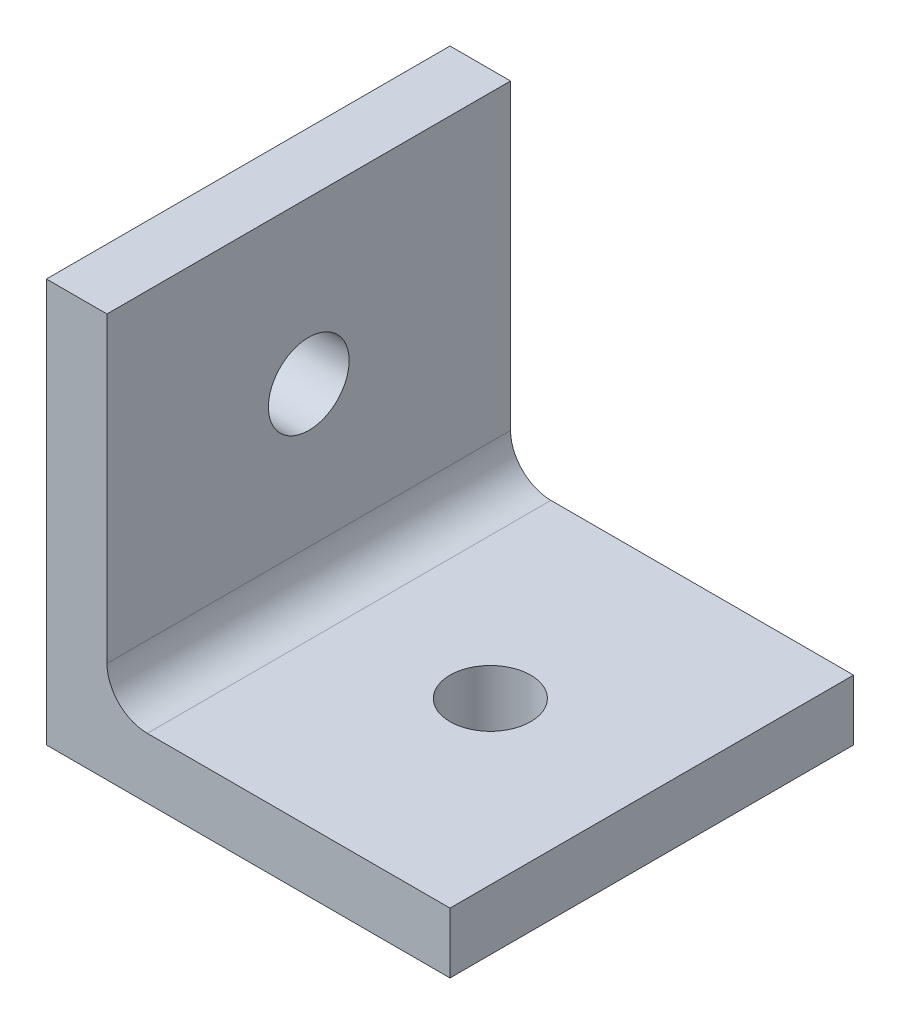
SolidWorks part; units mm, degrees
ref_plane "Płaszczyzna przednia" through (0, 0, 0) normal (0, 0, 1) x (1, 0, 0)
ref_plane "Płaszczyzna górna" through (0, 0, 0) normal (0, 1, 0) x (1, 0, 0)
ref_plane "Płaszczyzna prawa" through (0, 0, 0) normal (1, 0, 0) x (0, 0, -1)
sketch "Sketch1" plane through (0, 0, 0) normal (0, 0, 1) x (1, 0, 0)
  line L0 (3, 3) -> (20, 3)
  line L1 (0, 0) -> (3, 0)
  line L2 (0, 0) -> (0, 20)
  line L3 (0, 20) -> (3, 20)
  line L5 (0, 0) -> (3, 20) construction
  line L6 (0, 20) -> (3, 0) construction
  line L7 (0, 0) -> (20, 0)
  line L8 (0, 0) -> (0, 3)
  line L10 (20, 0) -> (20, 3)
  line L11 (0, 0) -> (20, 3) construction
  line L12 (0, 3) -> (20, 0) construction
  line L13 (3, 3) -> (3, 20)
  point P4 (1.5, 10)
  point P9 (10, 1.5)
  dimension "D1" = 20
  dimension "D2" = 20
  dimension "D3" = 3
  dimension "D4" = 3
extrude "Boss-Extrude1" add sketch "Sketch1" along normal blind 20 contours L0 L13 L3 L2 L1 L7 L10 region at (11.5, 2.7172, 0)
fillet "Fillet1" radius 2 1 edges at (3, 3, 10)
hole_wizard "Ø4.0mm Dowel Hole1" positions "Sketch2" profile "Sketch3" hole size "Ø4.0" standard "ANSI Metric" end condition through all
sketch "Sketch2" plane through (3, 0, 0) normal (1, 0, 0) x (0, 0, -1)
  line L0 (-20, 5) -> (-20, 20) construction
  line L2 (-20, 20) -> (0, 20) construction
  point P0 (-10, 12)
  point P9 (-13.7338, 20)
  dimension "D1" = 10
  dimension "D2" = 8
sketch "Sketch3" plane through (3, 12, 10) normal (0, 1, 0) x (0, 0, -1)
  line L0 (0, 0) -> (0, 3)
  line L1 (0, 3) -> (2, 3)
  line L2 (2, 3) -> (2, 0)
  line L5 (2, 0) -> (0, 0)
  line L11 (0, -6.35) -> (0, 107.95) construction
  dimension "Thru Hole Dia." = 4
  dimension "Thru Hole Depth" = 3
hole_wizard "Ø4.0mm Dowel Hole2" positions "Sketch4" profile "Sketch5" hole size "Ø4.0" standard "ANSI Metric" end condition through all
sketch "Sketch4" plane through (0, 3, 0) normal (0, 1, 0) x (1, 0, 0)
  line L0 (5, -20) -> (20, -20) construction
  line L2 (20, -20) -> (20, 0) construction
  point P0 (12, -10)
  point P9 (20, -10.3612)
  dimension "D1" = 10
  dimension "D2" = 8
sketch "Sketch5" plane through (12, 3, 10) normal (1, 0, 0) x (0, 0, 1)
  line L0 (0, 0) -> (0, 3)
  line L1 (0, 3) -> (2, 3)
  line L2 (2, 3) -> (2, 0)
  line L5 (2, 0) -> (0, 0)
  line L11 (0, -6.35) -> (0, 107.95) construction
  dimension "Thru Hole Dia." = 4
  dimension "Thru Hole Depth" = 3
